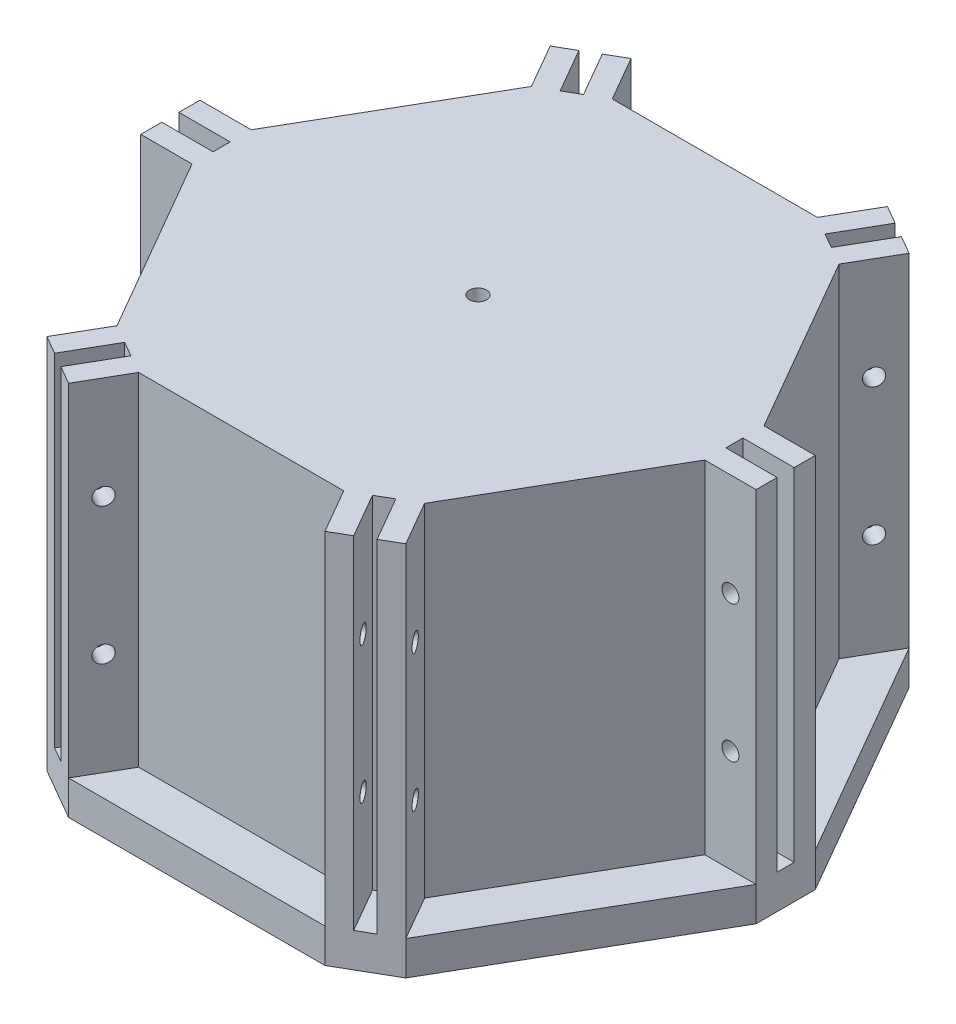
SolidWorks part; units mm, degrees
ref_plane "Front Plane" through (0, 0, 0) normal (0, 0, 1) x (1, 0, 0)
ref_plane "Top Plane" through (0, 0, 0) normal (0, 1, 0) x (1, 0, 0)
ref_plane "Right Plane" through (0, 0, 0) normal (1, 0, 0) x (0, 0, -1)
sketch "Sketch1" plane through (0, 0, 0) normal (0, 1, 0) x (1, 0, 0)
  line L1 (70, 0) -> (35, 60.6218)
  line L2 (35, 60.6218) -> (-35, 60.6218)
  line L3 (-35, 60.6218) -> (-70, 0)
  line L4 (-70, 0) -> (-35, -60.6218)
  line L5 (-35, -60.6218) -> (35, -60.6218)
  line L6 (35, -60.6218) -> (70, 0)
  circle A0 centre (0, 0) radius 60.6218 construction
  dimension "D1" = 70
  dimension "D2" = 60.6218
extrude "Boss-Extrude1" add sketch "Sketch1" along normal blind 100
sketch "Sketch2" plane through (0, 100, 0) normal (0, 1, 0) x (1, 0, 0)
  line L0 (35, 60.6218) -> (45, 77.9423) construction
  line L1 (52.4998, 73.6123) -> (37.5002, 82.2723)
  line L2 (37.5002, 82.2723) -> (24.7987, 60.2726)
  line L3 (52.4998, 73.6123) -> (39.7983, 51.6126)
  line L5 (24.7987, 60.2726) -> (39.7983, 51.6126)
  line L6 (0, 0) -> (35, 60.6218) construction
  point P6 (45, 77.9423)
  dimension "D1" = 20
  dimension "D2" = 17.32
  dimension "D3" = 25.403
  dimension "D4" = 25.403
  dimension "D5" = 90
extrude "Boss-Extrude2" add sketch "Sketch2" against normal blind 100
ref_axis "Axis1" through (0, -5, 0) along (0, 1, 0)
pattern_circular "CirPattern1" count 6 over 360 about axis through (0, -5, 0) along (0, 1, 0) of "Boss-Extrude2"
sketch "Sketch3" plane through (90, 0, 0) normal (1, 0, 0) x (0, 0, -1)
  line L0 (0, 100) -> (0, 0) construction
  line L1 (-8.66, 100) -> (8.66, 100) construction
  line L3 (2.5, 0) -> (-2.5, 0)
  line L4 (2.5, 0) -> (2.5, 100)
  line L5 (2.5, 100) -> (-2.5, 100)
  line L6 (-2.5, 0) -> (-2.5, 100)
  line L7 (2.5, 0) -> (-2.5, 100) construction
  line L8 (2.5, 100) -> (-2.5, 0) construction
  point P5 (0, 50)
  dimension "D1" = 5
extrude "Cut-Extrude1" cut sketch "Sketch3" against normal blind 15
pattern_circular "CirPattern2" count 6 over 360 about axis through (0, -5, 0) along (0, 1, 0) of "Cut-Extrude1"
sketch "Sketch4" plane through (0, 0, 0) normal (0, -1, 0) x (1, 0, 0)
  line L0 (-52.4998, 73.6123) -> (-37.5002, 82.2723)
  line L1 (-37.5002, 82.2723) -> (37.5002, 82.2723)
  line L2 (37.5002, 82.2723) -> (52.4998, 73.6123)
  line L3 (52.4998, 73.6123) -> (90, 8.66)
  line L4 (90, 8.66) -> (90, -8.66)
  line L5 (90, -8.66) -> (52.4998, -73.6123)
  line L6 (52.4998, -73.6123) -> (37.5002, -82.2723)
  line L7 (37.5002, -82.2723) -> (-37.5002, -82.2723)
  line L8 (-37.5002, -82.2723) -> (-52.4998, -73.6123)
  line L9 (-52.4998, -73.6123) -> (-90, -8.66)
  line L10 (-90, -8.66) -> (-90, 8.66)
  line L11 (-90, 8.66) -> (-52.4998, 73.6123)
  line L13 (50, 0) -> (25, 43.3013)
  line L14 (25, 43.3013) -> (-25, 43.3013)
  line L15 (-25, 43.3013) -> (-50, 0)
  line L16 (-50, 0) -> (-25, -43.3013)
  line L17 (-25, -43.3013) -> (25, -43.3013)
  line L18 (25, -43.3013) -> (50, 0)
  circle A0 centre (0, 0) radius 43.3013 construction
  dimension "D1" = 50
  dimension "D2" = 43.3013
extrude "Boss-Extrude3" add sketch "Sketch4" along normal blind 10
sketch "Sketch5" plane through (0, 100, 0) normal (0, 1, 0) x (1, 0, 0)
  circle A0 centre (0, 0) radius 2.5
  dimension "D1" = 5
extrude "Cut-Extrude2" cut sketch "Sketch5" against normal blind 200
sketch "Sketch6" plane through (0, 0, 8.66) normal (0, 0, 1) x (1, 0, 0)
  line L0 (65.0001, 100) -> (90, 100) construction
  line L1 (65.0001, 0) -> (90, 0) construction
  line L2 (90, 0) -> (90, 100) construction
  circle A0 centre (82.5, 70) radius 2.5
  circle A1 centre (82.5, 30) radius 2.5
  dimension "D1" = 5
  dimension "D2" = 5
  dimension "D3" = 30
  dimension "D4" = 30
  dimension "D5" = 7.5
  dimension "D6" = 7.5
extrude "Cut-Extrude3" cut sketch "Sketch6" against normal through all
pattern_circular "CirPattern3" count 6 every 60 about axis through (0, -5, 0) along (0, 1, 0) of "Cut-Extrude3"
sketch "Sketch7" plane through (0, 0, 0) normal (0, 1, 0) x (1, 0, 0)
  line L0 (-65.0001, 8.66) -> (-39.9999, 51.9618)
  line L2 (-39.9999, 51.9618) -> (-44.9997, 60.6218)
  line L3 (-52.4998, 73.6123) -> (-39.9999, 51.9618) construction
  line L4 (-44.9997, 60.6218) -> (-74.9999, 8.66)
  line L5 (-65.0001, 8.66) -> (-90, 8.66) construction
  line L6 (-74.9999, 8.66) -> (-65.0001, 8.66)
  dimension "D1" = 8.66
extrude "Boss-Extrude4" add sketch "Sketch7" along normal blind 100
pattern_circular "CirPattern4" count 6 every 60 about axis through (0, -5, 0) along (0, 1, 0) of "Boss-Extrude4"
sketch "Sketch8" plane through (0, 0, 0) normal (0, -1, 0) x (1, 0, 0)
  line L1 (50, 0) -> (25, 43.3013)
  line L2 (25, 43.3013) -> (-25, 43.3013)
  line L3 (-25, 43.3013) -> (-50, 0)
  line L4 (-50, 0) -> (-25, -43.3013)
  line L5 (-25, -43.3013) -> (25, -43.3013)
  line L6 (25, -43.3013) -> (50, 0)
  circle A0 centre (0, 0) radius 43.3013 construction
  dimension "D1" = 43.3013
  dimension "D2" = 50
extrude "Boss-Extrude5" add sketch "Sketch8" along normal blind 10
sketch "Sketch9" plane through (0, 100, 0) normal (0, 1, 0) x (1, 0, 0)
  circle A0 centre (0, 0) radius 2.5
  dimension "D1" = 5
extrude "Cut-Extrude4" cut sketch "Sketch9" against normal through all
sketch "Sketch10" plane through (0, 100, 0) normal (0, 1, 0) x (1, 0, 0)
  line L0 (2.02, 1.473) -> (2.02, -1.473)
  arc A0 (2.02, -1.473) -> (2.02, 1.473) centre (0, 0) ccw
  dimension "D1" = 0.48
